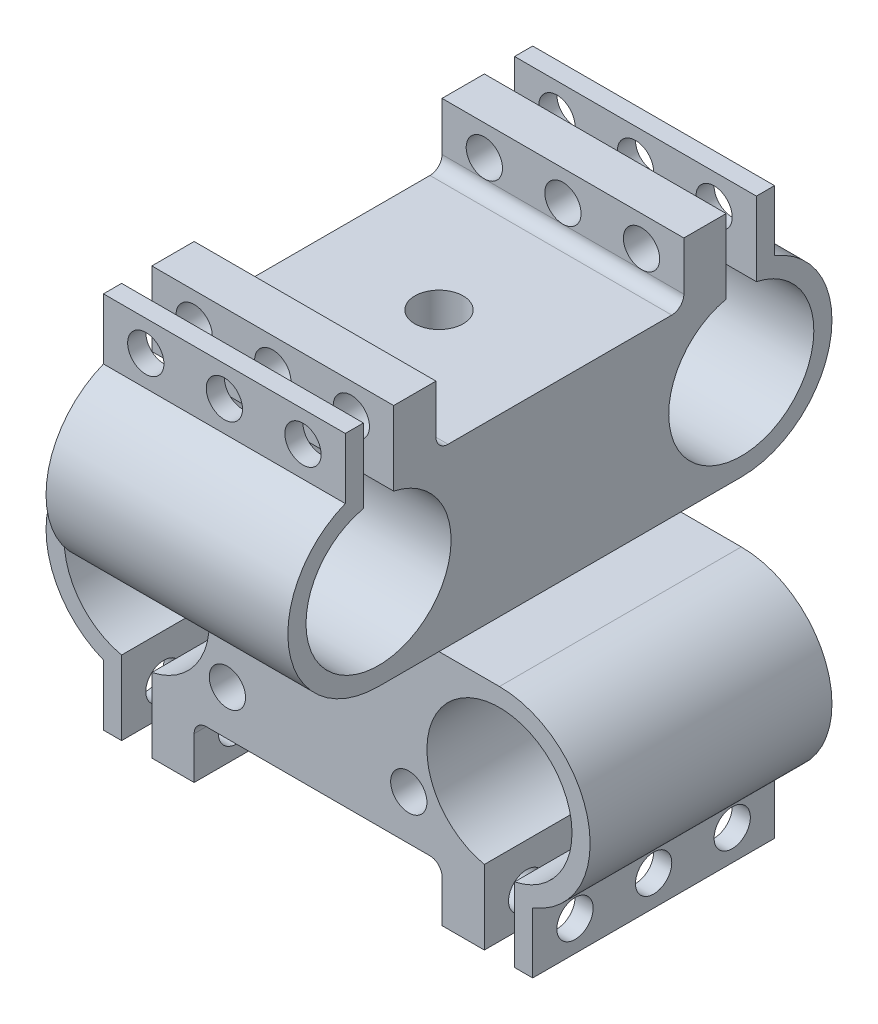
SolidWorks part; units mm, degrees
ref_plane "정면" through (0, 0, 0) normal (0, 0, 1) x (1, 0, 0)
ref_plane "윗면" through (0, 0, 0) normal (0, 1, 0) x (1, 0, 0)
ref_plane "우측면" through (0, 0, 0) normal (1, 0, 0) x (0, 0, -1)
sketch "스케치1" plane through (0, 0, 0) normal (1, 0, 0) x (0, 0, -1)
  line L0 (0, 7.5) -> (0, -7.5) construction
  line L1 (-12.25, 0) -> (12.25, 0) construction
  line L2 (-15, 0) -> (15, 0) construction
  line L3 (-17.75, 12) -> (-16.25, 12)
  line L4 (-17.75, 12) -> (-17.75, 5.3327)
  line L5 (-12.75, 0) -> (12.75, 0) construction
  line L6 (-12.25, 12) -> (-12.25, 5.3327)
  line L7 (-17.75, -0.0455) -> (-12.25, 0) construction
  line L8 (12.25, 12) -> (12.25, 0) construction
  line L9 (12.25, 12) -> (12.25, 5.3327)
  line L10 (17.75, 12) -> (17.75, 5.3327)
  line L11 (17.75, 12) -> (16.25, 12)
  line L12 (-13.75, 10.5) -> (-13.75, 5.8683)
  line L13 (13.75, 10.5) -> (13.75, 1.5) construction
  line L14 (-16.25, 10.5) -> (-16.25, 5.8683)
  line L15 (13.75, 12) -> (12.25, 12)
  line L16 (13.75, 10.5) -> (13.75, 5.8683)
  line L17 (-12.25, 6.9776) -> (12.25, 6.9776)
  line L18 (16.25, 10.5) -> (16.25, 5.8683)
  line L19 (16.25, 10.5) -> (16.25, 1.5) construction
  line L20 (-16.25, 10.5) -> (-16.25, 12)
  line L21 (-13.75, 10.5) -> (-13.75, 12)
  line L22 (13.75, 10.5) -> (13.75, 12)
  line L23 (16.25, 10.5) -> (16.25, 12)
  line L24 (-16.25, 10.5) -> (-13.75, 10.5) construction
  line L25 (-13.75, 12) -> (-12.25, 12)
  line L26 (-17.75, 12) -> (-12.25, 12) construction
  line L27 (16.25, 10.5) -> (13.75, 10.5) construction
  line L28 (17.75, 12) -> (12.25, 12) construction
  line L29 (-15, -7.5) -> (15, -7.5)
  line L30 (17.75, 12) -> (17.75, 0) construction
  line L31 (-17.75, 12) -> (-17.75, -0.0455) construction
  line L33 (-16.25, 10.5) -> (-16.25, 1.467) construction
  line L35 (-13.75, 10.5) -> (-13.75, 1.4876) construction
  line L36 (-12.25, 12) -> (-12.25, 0) construction
  line L37 (-16.25, 1.467) -> (-13.75, 1.4876) construction
  line L38 (16.25, 1.5) -> (13.75, 1.5) construction
  line L39 (17.75, 0) -> (12.25, 0) construction
  arc A0 (-16.25, 5.8683) -> (-13.75, 5.8683) centre (-15, 0) ccw
  arc A1 (16.25, 5.8683) -> (13.75, 5.8683) centre (15, 0) cw
  arc A2 (-16.25, 7.3951) -> (-13.75, 7.3951) centre (-15, 0) ccw
  arc A3 (16.25, 7.3951) -> (13.75, 7.3951) centre (15, 0) cw
  circle A4 centre (-15, 0) radius 6 construction
  circle A5 centre (-15, 0) radius 7.5 construction
  point P3 (0, 0)
  point P12 (-15, 6)
  dimension "D1" = 12
  dimension "D2" = 30
  dimension "D4" = 12
  dimension "D5" = 5.5
  dimension "D7" = 6.6673
  dimension "D3" = 1.5
  dimension "D6" = 1.5
extrude "보스-돌출1" add sketch "스케치1" along normal blind 20 contours L29 A3 L17 A2 | L4 A2 L6 A0 | L6 A2 L12 A0 | L14 A2 L4 A0 | A2 L14 L20 L3 L4 | A2 L6 L25 L21 L12 | A3 L10 A1 L9 | A3 L18 A1 L10 | L18 A3 L10 L11 L23 | L9 A3 L16 L22 L15 | A3 L9 A1 L16 region at (0, 9.6057, 17.0109) region at (0, 6.4233, 17.0093) region at (0, 6.1552, 17.9585) region at (0, -0.3836, 0) region at (0, 6.4233, 12.9907) region at (0, -1.3607, -7.8366) region at (0, 9.6057, 12.9891) region at (0, 6.4233, -12.9907) region at (0, 9.6057, -12.9891) region at (0, 9.6057, -17.0109) region at (0, 6.4233, -17.0093)
sketch "스케치2" plane through (0, 0, 17.75) normal (0, 0, 1) x (1, 0, 0)
  line L0 (0, 9.4888) -> (20, 9.4888) construction
  line L1 (10, 12) -> (10, 6.9776) construction
  line L2 (3.5, 12) -> (3.5, 6.9776) construction
  line L3 (16.5, 12) -> (16.5, 6.9776) construction
  line L4 (0, 12) -> (0, 6.9776)
  line L5 (0, 6.9776) -> (20, 6.9776)
  line L6 (20, 6.9776) -> (20, 12)
  line L7 (20, 12) -> (0, 12)
  line L8 (0, 12) -> (0, 6.9776)
  line L9 (0, 6.9776) -> (20, 6.9776)
  line L10 (20, 6.9776) -> (20, 12)
  line L11 (20, 12) -> (0, 12)
  circle A0 centre (3.5, 9.4888) radius 1.5
  circle A1 centre (16.5, 9.4888) radius 1.5
  circle A2 centre (10, 9.4888) radius 1.5
  point P14 (3.5, 9.4888)
  point P17 (16.5, 9.4888)
  dimension "D3" = 3
  dimension "D2" = 6.5
  dimension "D1" = 0
extrude "컷-돌출1" cut sketch "스케치2" against normal through all contours A0 | A2 | A1 region at (3.5, 9.4888, 17.75) region at (10, 9.4888, 17.75)
sketch "스케치5" plane through (0, 0, 0) normal (0, 0, 1) x (1, 0, 0)
  line L0 (-72.0207, -10.4098) -> (-72.0207, -25.4098) construction
  line L1 (-84.2707, -17.9098) -> (-59.7707, -17.9098) construction
  line L2 (-87.0207, -17.9098) -> (-57.0207, -17.9098) construction
  line L3 (-89.7707, -5.9098) -> (-88.2707, -5.9098)
  line L4 (-89.7707, -5.9098) -> (-89.7707, -12.5771)
  line L5 (-84.7707, -17.9098) -> (-59.2707, -17.9098) construction
  line L6 (-84.2707, -5.9098) -> (-84.2707, -12.5771)
  line L7 (-59.7707, -5.9098) -> (-59.7707, -12.5771)
  line L8 (-54.2707, -5.9098) -> (-54.2707, -12.5771)
  line L9 (-54.2707, -5.9098) -> (-55.7707, -5.9098)
  line L10 (-85.7707, -7.4098) -> (-85.7707, -12.0415)
  line L11 (-88.2707, -7.4098) -> (-88.2707, -12.0415)
  line L12 (-58.2707, -5.9098) -> (-59.7707, -5.9098)
  line L13 (-58.2707, -7.4098) -> (-58.2707, -12.0415)
  line L14 (-84.2707, -10.9322) -> (-59.7707, -10.9322)
  line L15 (-55.7707, -7.4098) -> (-55.7707, -12.0415)
  line L16 (-88.2707, -7.4098) -> (-88.2707, -5.9098)
  line L17 (-85.7707, -7.4098) -> (-85.7707, -5.9098)
  line L18 (-58.2707, -7.4098) -> (-58.2707, -5.9098)
  line L19 (-55.7707, -7.4098) -> (-55.7707, -5.9098)
  line L20 (-85.7707, -5.9098) -> (-84.2707, -5.9098)
  line L21 (-87.0207, -25.4098) -> (-57.0207, -25.4098)
  line L22 (20, -7.5) -> (0, -7.5) construction
  line L23 (25, -7.5) -> (-5, -7.5)
  line L24 (25, -7.5) -> (25, -22.5) construction
  line L25 (25, -22.5) -> (-5, -22.5)
  line L26 (-5, -7.5) -> (-5, -22.5) construction
  line L27 (20, -7.5) -> (0, -7.5)
  line L28 (-2.25, -20.3327) -> (-2.25, -27.0027)
  line L29 (-7.75, -20.3327) -> (-6.25, -20.3327)
  line L30 (-7.75, -20.3327) -> (-7.75, -27.0027)
  line L31 (-7.75, -27.0027) -> (-6.25, -27.0027)
  line L32 (-6.25, -20.3327) -> (-6.25, -27.0027)
  line L33 (-2.25, -20.3327) -> (-3.75, -20.3327)
  line L34 (-3.75, -20.3327) -> (-3.75, -27.0027)
  line L35 (-2.25, -27.0027) -> (-3.75, -27.0027)
  line L36 (10, -7.5) -> (10, -22.5) construction
  line L37 (22.25, -20.3327) -> (23.75, -20.3327)
  line L38 (27.75, -20.3327) -> (26.25, -20.3327)
  line L39 (27.75, -20.3327) -> (27.75, -27.0027)
  line L40 (22.25, -20.3327) -> (22.25, -27.0027)
  line L41 (23.75, -20.3327) -> (23.75, -27.0027)
  line L42 (26.25, -20.3327) -> (26.25, -27.0027)
  line L43 (22.25, -27.0027) -> (23.75, -27.0027)
  line L44 (27.75, -27.0027) -> (26.25, -27.0027)
  arc A0 (-88.2707, -12.0415) -> (-85.7707, -12.0415) centre (-87.0207, -17.9098) ccw
  arc A1 (-55.7707, -12.0415) -> (-58.2707, -12.0415) centre (-57.0207, -17.9098) cw
  arc A2 (-88.2707, -10.5147) -> (-85.7707, -10.5147) centre (-87.0207, -17.9098) ccw
  arc A3 (-55.7707, -10.5147) -> (-58.2707, -10.5147) centre (-57.0207, -17.9098) cw
  circle A4 centre (-5, -15) radius 7.5
  circle A5 centre (25, -15) radius 7.5
  circle A6 centre (-5, -15) radius 6
  circle A7 centre (25, -15) radius 6
  point P2 (-72.0207, -17.9098)
  point P11 (-87.0207, -11.9098)
  point P44 (10, -7.5)
  point P47 (10, -7.5)
  point P72 (-7.75, -21.9776)
  point P73 (-6.25, -19.1657)
  point P74 (-3.75, -22.3951)
  point P75 (-2.25, -21.4476)
  point P76 (22.25, -21.9776)
  point P77 (23.75, -22.3951)
  point P78 (26.25, -22.3951)
  point P79 (27.75, -21.9776)
  dimension "D4" = 6
  dimension "D5" = 7.5
  dimension "D10" = 12
  dimension "D1" = 24.5
  dimension "D2" = 30
  dimension "D3" = 30
  dimension "D6" = 6.6673
  dimension "D7" = 1.5
  dimension "D8" = 30
  dimension "D9" = 15
  dimension "D11" = 1.5
  dimension "D12" = 6.67
  dimension "D13" = 2.5
  dimension "D14" = 2.5
extrude "보스-돌출2" add sketch "스케치5" along normal mid plane 20 contours A7 L39 A5 L40 | A7 L40 A5 L41 | A7 L42 A5 L39 | A5 L42 L44 L39 | A5 L40 L25 L41 | L40 L43 L41 L25 | A5 L23 A4 L28 L25 L40 | A6 L28 A4 L30 | A6 L30 A4 L32 | A4 L30 L31 L32 | A4 L34 L25 L28 | L35 L28 L25 L34 | A6 L34 A4 L28 region at (10, -14.9745, 0) region at (30.1559, -9.8441, 0) region at (22.8177, -22.3316, 0) region at (22.9907, -21.4233, 0) region at (27.0093, -21.4233, 0) region at (27.0109, -24.607, 0) region at (23, -24.7513, 0) region at (0.1559, -9.8441, 0) region at (-3, -24.7513, 0) region at (-2.8177, -22.3316, 0) region at (-7.0109, -24.607, 0) region at (-7.0093, -21.4233, 0) region at (-2.9907, -21.4233, 0)
sketch "스케치6" plane through (27.75, 0, 0) normal (1, 0, 0) x (0, 0, -1)
  line L0 (0, 0) -> (0, -27.0027) construction
  line L1 (-10, -24.4902) -> (10, -24.4902) construction
  line L4 (10, -27.0027) -> (10, -21.9776)
  line L5 (10, -21.9776) -> (-10, -21.9776)
  line L6 (-10, -21.9776) -> (-10, -27.0027)
  line L7 (-10, -27.0027) -> (10, -27.0027)
  line L8 (10, -27.0027) -> (10, -21.9776)
  line L9 (10, -21.9776) -> (-10, -21.9776)
  line L10 (-10, -21.9776) -> (-10, -27.0027)
  line L11 (-10, -27.0027) -> (10, -27.0027)
  circle A0 centre (-6.5, -24.4902) radius 1.5
  circle A1 centre (6.5, -24.4902) radius 1.5
  circle A2 centre (0, -24.4902) radius 1.5
  dimension "D3" = 3
  dimension "D2" = 6.5
  dimension "D1" = 0
extrude "컷-돌출2" cut sketch "스케치6" against normal through all contours A0 | A2 | A1 region at (27.75, -24.4902, 6.5) region at (27.75, -24.4902, -6.5) region at (27.75, -24.4902, 0)
sketch "스케치7" plane through (0, 6.9776, 0) normal (0, 1, 0) x (1, 0, 0)
  line L0 (0, 0) -> (20, 0) construction
  line L1 (20, -12.25) -> (20, 12.25) construction
  line L2 (10, 12.25) -> (10, -12.25) construction
  line L3 (20, 12.25) -> (0, 12.25) construction
  line L4 (20, -12.25) -> (0, -12.25) construction
  circle A0 centre (10, 0) radius 2
  dimension "D1" = 4
extrude "컷-돌출3" cut sketch "스케치7" against normal through all
sketch "스케치8" plane through (0, -22.5, 0) normal (0, -1, 0) x (1, 0, 0)
  circle A0 centre (10, 0) radius 6
  circle A1 centre (10, 0) radius 8
  dimension "D1" = 12
  dimension "D2" = 16
extrude "컷-돌출4" cut sketch "스케치8" against normal blind 10 contours A1
sketch "스케치9" plane through (0, 0, 10) normal (0, 0, 1) x (1, 0, 0)
  line L0 (10, -7.5) -> (10, -22.5) construction
  line L1 (20, -7.5) -> (0, -7.5) construction
  line L2 (22.25, -22.5) -> (-2.25, -22.5) construction
  circle A0 centre (17.5, -18.8) radius 1.5
  circle A1 centre (2.5, -18.8) radius 1.5
  dimension "D1" = 3
  dimension "D2" = 15
  dimension "D3" = 3.7
extrude "컷-돌출5" cut sketch "스케치9" against normal through all
sketch "스케치10" plane through (0, 0, -12.25) normal (0, 0, 1) x (1, 0, 0)
  line L4 (0, 12) -> (0, 6.9776)
  line L5 (0, 6.9776) -> (20, 6.9776)
  line L6 (20, 6.9776) -> (20, 12)
  line L7 (20, 12) -> (0, 12)
  line L8 (0, 12) -> (0, 6.9776)
  line L9 (0, 6.9776) -> (20, 6.9776)
  line L10 (20, 6.9776) -> (20, 12)
  line L11 (20, 12) -> (0, 12)
  circle A0 centre (3.5, 9.4888) radius 1.5 construction
  circle A1 centre (10, 9.4888) radius 1.5 construction
  circle A2 centre (16.5, 9.4888) radius 1.5 construction
  circle A3 centre (3.5, 9.4888) radius 1.5
  circle A4 centre (10, 9.4888) radius 1.5
  circle A5 centre (16.5, 9.4888) radius 1.5
  dimension "D1" = 0
extrude "보스-돌출3" add sketch "스케치10" along normal blind 2
mirror "대칭 복사1" about plane through (0, 0, 0) normal (0, 0, 1) of "보스-돌출3"
fillet "필렛1" radius 1 2 edges at (10, 6.9776, -10.25) (10, 6.9776, 10.25)
sketch "스케치11" plane through (22.25, 0, 0) normal (-1, 0, 0) x (0, 0, 1)
  line L4 (-10, -22.5) -> (-10, -27.0027)
  line L5 (-10, -27.0027) -> (10, -27.0027)
  line L6 (10, -27.0027) -> (10, -22.5)
  line L7 (10, -22.5) -> (-10, -22.5)
  line L8 (-10, -22.5) -> (-10, -27.0027)
  line L9 (-10, -27.0027) -> (10, -27.0027)
  line L10 (10, -27.0027) -> (10, -22.5)
  line L11 (10, -22.5) -> (-10, -22.5)
  circle A0 centre (0, -24.4902) radius 1.5 construction
  circle A1 centre (6.5, -24.4902) radius 1.5 construction
  circle A2 centre (0, -24.4902) radius 1.5
  circle A3 centre (6.5, -24.4902) radius 1.5
  circle A4 centre (-6.5, -24.4902) radius 1.5 construction
  circle A5 centre (-6.5, -24.4902) radius 1.5
  dimension "D1" = 0
extrude "보스-돌출4" add sketch "스케치11" along normal blind 2
ref_plane "평면1" through (10, 0, 0) normal (-1, 0, 0) x (0, 0, 1)
mirror "대칭 복사2" about plane through (10, 0, 0) normal (-1, 0, 0) of "보스-돌출4"
chamfer "모따기1" distance 1 angle 45 1 edges at (10, -22.5, -8)
fillet "필렛2" radius 1 2 edges at (-0.25, -22.5, 0) (20.25, -22.5, 0)
